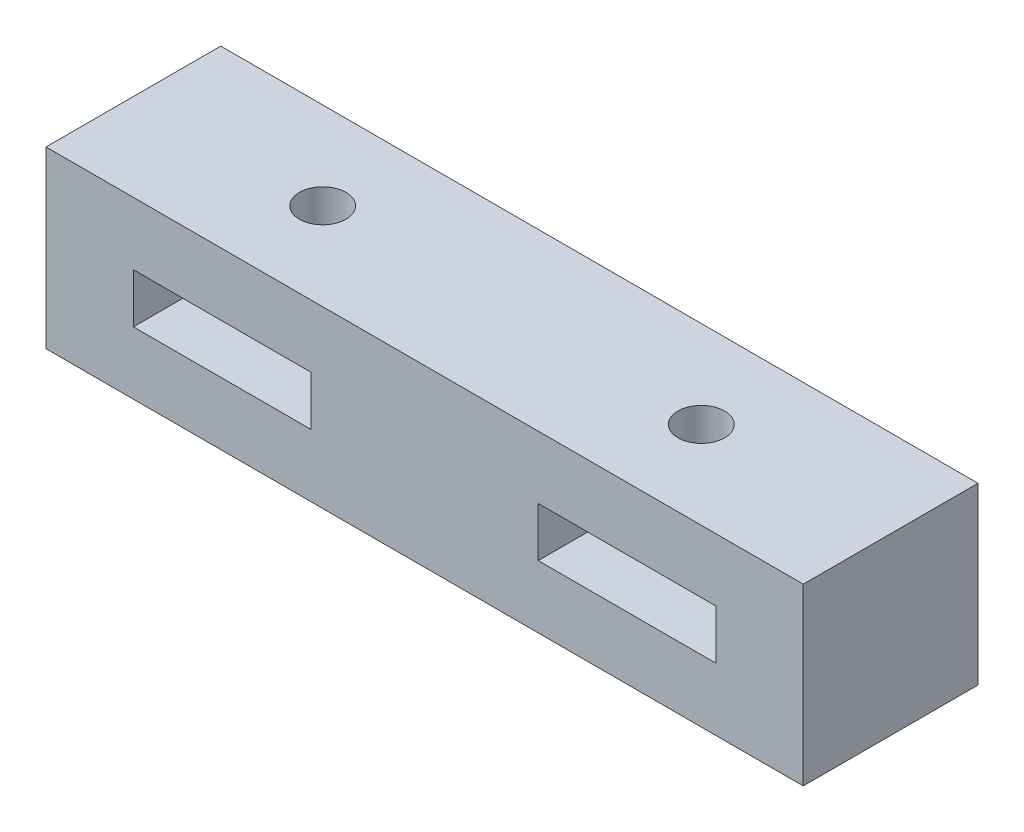
SolidWorks part; units mm, degrees
ref_plane "Alzado" through (0, 0, 0) normal (0, 0, 1) x (1, 0, 0)
ref_plane "Planta" through (0, 0, 0) normal (0, 1, 0) x (1, 0, 0)
ref_plane "Vista lateral" through (0, 0, 0) normal (1, 0, 0) x (0, 0, -1)
sketch "Croquis1" plane through (0, 0, 0) normal (0, 0, 1) x (1, 0, 0)
  line L0 (0, 0) -> (-26, 0) construction
  line L1 (-26, -6) -> (26, -6)
  line L2 (-26, -6) -> (-26, 6)
  line L3 (-26, 6) -> (26, 6)
  line L4 (26, -6) -> (26, 6)
  line L5 (-26, -6) -> (26, 6) construction
  line L6 (-26, 6) -> (26, -6) construction
  line L7 (0, 6) -> (0, -6) construction
  line L8 (20, 1.7) -> (7.8, 1.7)
  line L9 (-20, -1.7) -> (-7.8, -1.7)
  line L10 (-20, -1.7) -> (-20, 1.7)
  line L11 (-20, 1.7) -> (-7.8, 1.7)
  line L12 (-7.8, -1.7) -> (-7.8, 1.7)
  line L13 (-20, -1.7) -> (-7.8, 1.7) construction
  line L14 (-20, 1.7) -> (-7.8, -1.7) construction
  line L15 (7.8, -1.7) -> (7.8, 1.7)
  line L16 (20, -1.7) -> (7.8, -1.7)
  line L17 (20, -1.7) -> (20, 1.7)
  point P0 (0, 0)
  point P10 (-13.9, 0)
  dimension "D1" = 12
  dimension "D2" = 52
  dimension "D3" = 20
  dimension "D4" = 12.2
  dimension "D5" = 3.4
extrude "Saliente-Extruir1" add sketch "Croquis1" along normal mid plane 12
sketch "Croquis2" plane through (0, 0, -6) normal (0, 0, -1) x (-1, 0, 0)
  circle A0 centre (0, 0) radius 4.2188
  dimension "D1" = 8.4375
extrude "Cortar-Extruir1" cut sketch "Croquis2" against normal blind 11
sketch "Croquis3" plane through (0, 6, 0) normal (0, 1, 0) x (1, 0, 0)
  line L0 (-13, 6) -> (-13, -6) construction
  line L1 (26, 6) -> (-26, 6) construction
  line L2 (26, -6) -> (-26, -6) construction
  line L3 (0, 6) -> (0, -6) construction
  circle A0 centre (-13, 0) radius 1.6
  circle A1 centre (13, 0) radius 1.6
  dimension "D2" = 3.2
  dimension "D1" = 13
extrude "Cortar-Extruir2" cut sketch "Croquis3" against normal blind 30
